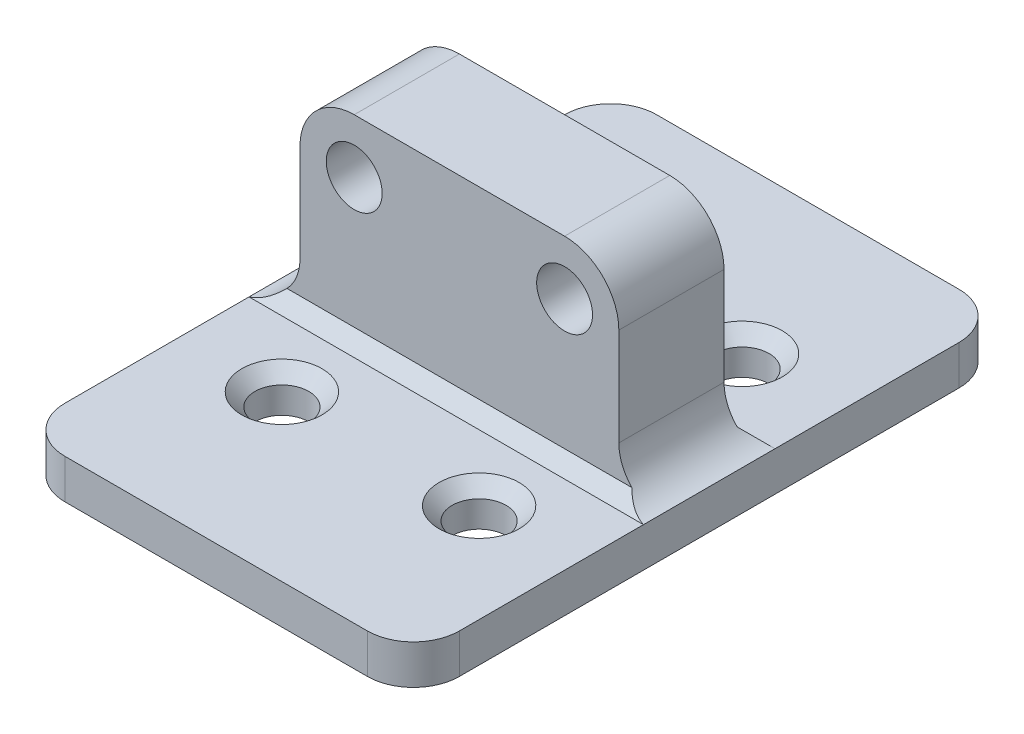
SolidWorks part; units mm, degrees
ref_plane "Front Plane" through (0, 0, 0) normal (0, 0, 1) x (1, 0, 0)
ref_plane "Top Plane" through (0, 0, 0) normal (0, 1, 0) x (1, 0, 0)
ref_plane "Right Plane" through (0, 0, 0) normal (1, 0, 0) x (0, 0, -1)
sketch "Sketch1" plane through (0, 0, 0) normal (0, 1, 0) x (1, 0, 0)
  line L1 (-15, -22.5) -> (15, -22.5)
  line L2 (-15, -22.5) -> (-15, 22.5)
  line L3 (-15, 22.5) -> (15, 22.5)
  line L4 (15, -22.5) -> (15, 22.5)
  line L5 (-15, -22.5) -> (15, 22.5) construction
  line L6 (-15, 22.5) -> (15, -22.5) construction
  point P0 (0, 0)
  point P6 (0, 0)
  line B0 (-7.5, -10) -> (-7.5, 10) construction
  circle B1 centre (-7.5, 10) radius 2.05
  circle B2 centre (7.5, 10) radius 2.05
  circle B3 centre (-7.5, -10) radius 2.05
  circle B4 centre (7.5, -10) radius 2.05
  dimension "D1" = 30
  dimension "D2" = 45
sketch_block_instance "Block1-1"
sketch_block "Block1" parameters "D1"=4.1, "D2"=20, "D3"=15
extrude "Boss-Extrude1" add sketch "Sketch1" along normal blind 3
fillet "Fillet1" radius 3.5 4 edges at (-15, 1.5, 22.5) (15, 1.5, -22.5) (-15, 1.5, -22.5) (15, 1.5, 22.5)
sketch "Sketch2" plane through (0, 0, 0) normal (0, 0, 1) x (1, 0, 0)
  line L0 (0, 0) -> (12.125, 0)
  line L1 (-11.5, 0) -> (11.5, 0) construction
  line L2 (12.125, 0) -> (12.125, 13.875)
  line L3 (8, 18) -> (-8, 18)
  line L4 (-12.125, 13.875) -> (-12.125, 0)
  line L5 (-12.125, 0) -> (0, 0)
  line L6 (-8, 13.875) -> (8, 13.875) construction
  line L7 (15, 3) -> (11.5, 3) construction
  arc A1 (-8, 18) -> (-12.125, 13.875) centre (-8, 13.875) ccw
  arc A2 (8, 18) -> (12.125, 13.875) centre (8, 13.875) cw
  circle A3 centre (-8, 13.875) radius 2.125
  circle A4 centre (8, 13.875) radius 2.125
  point P11 (0, 18)
  point P16 (0, 13.875)
  point P18 (9.6789, 10.3779)
  point P19 (-8, 8.0712)
  point P20 (-9.933, 11.665)
  point P23 (0, 0)
  point P24 (-8, 15.433)
  point P25 (0, 0)
  point P26 (0, 0)
  point P27 (0, 0)
  point P28 (-11.839, 14.161)
  dimension "D2" = 4.25
  dimension "D3" = 2
  dimension "D1" = 16
  dimension "D4" = 15
extrude "Boss-Extrude2" add sketch "Sketch2" along normal mid plane 8
fillet "Fillet2" radius 3.5 2 edges at (12.125, 3, 0) (-12.125, 3, 0)
chamfer "Chamfer1" distance 1 angle 45 6 edges at (0, 3, 4) (0, 3, -4) (7.5, 3, -7.95) (-7.5, 3, -7.95) (7.5, 3, 12.05) (-7.5, 3, 12.05)
